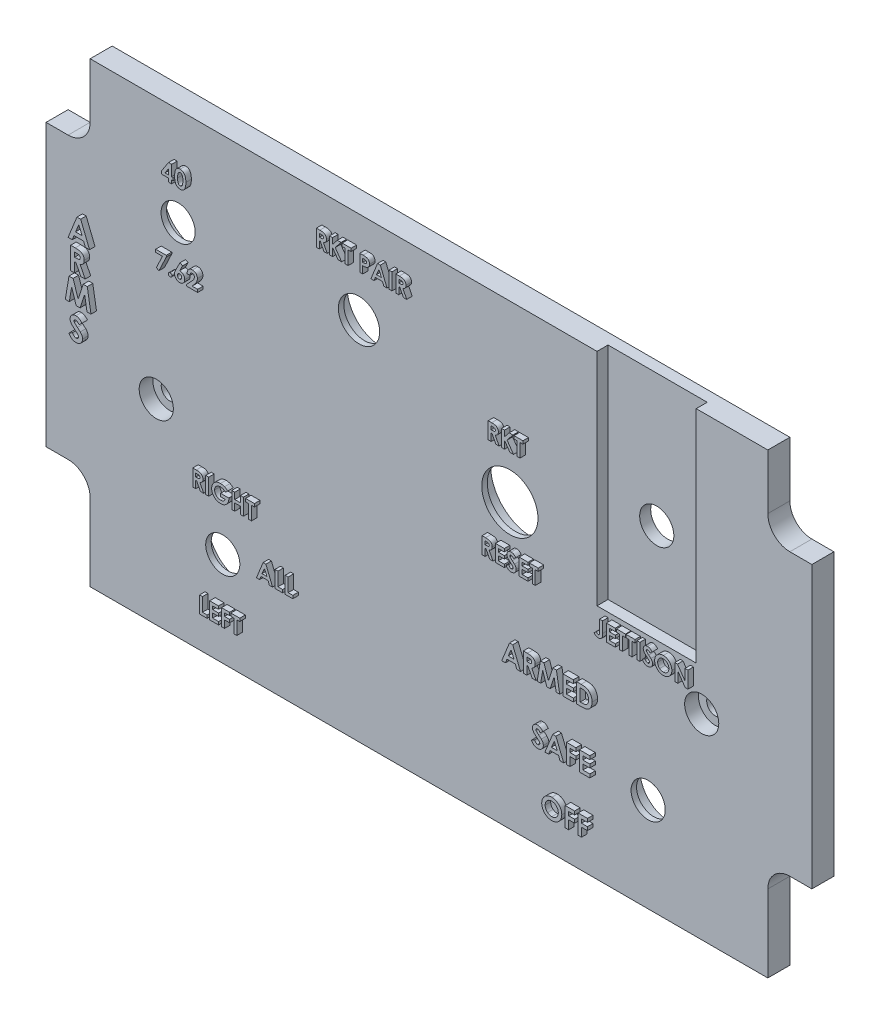
SolidWorks part; units mm, degrees
ref_plane "Front Plane" through (0, 0, 0) normal (0, 0, 1) x (1, 0, 0)
ref_plane "Top Plane" through (0, 0, 0) normal (0, 1, 0) x (1, 0, 0)
ref_plane "Right Plane" through (0, 0, 0) normal (1, 0, 0) x (0, 0, -1)
sketch "Sketch1" plane through (0, 0, 0) normal (0, 0, 1) x (1, 0, 0)
  line L1 (8, 6.6454) -> (131, 6.6454)
  line L2 (0, 24.6454) -> (0, 75.6454)
  line L3 (8, 89.6454) -> (131, 89.6454)
  line L4 (139, 24.6454) -> (139, 75.6454)
  line L13 (8, 89.6454) -> (8, 79.6454)
  line L14 (4, 75.6454) -> (0, 75.6454)
  line L15 (8, 6.6454) -> (8, 20.6454)
  line L16 (4, 24.6454) -> (0, 24.6454)
  line L17 (131, 89.6454) -> (131, 79.6454)
  line L18 (135, 75.6454) -> (139, 75.6454)
  line L19 (131, 6.6454) -> (131, 20.6454)
  line L20 (135, 24.6454) -> (139, 24.6454)
  line L23 (0, 0) -> (0, 87.0008) construction
  arc A8 (8, 20.6454) -> (4, 24.6454) centre (4, 20.6454) ccw
  arc A9 (8, 79.6454) -> (4, 75.6454) centre (4, 79.6454) cw
  arc A11 (131, 20.6454) -> (135, 24.6454) centre (135, 20.6454) cw
  arc A12 (131, 79.6454) -> (135, 75.6454) centre (135, 79.6454) ccw
  circle A14 centre (119, 42.1736) radius 1.6 construction
  circle A15 centre (109.2813, 23.7457) radius 3.1 construction
  circle A16 centre (108.8427, 65.6454) radius 3.1 construction
  circle A17 centre (84.179, 58.026) radius 5.1 construction
  circle A18 centre (56.7976, 72.9728) radius 3.75 construction
  circle A19 centre (32.0701, 23.7457) radius 3.1 construction
  circle A35 centre (20, 42.1736) radius 1.6 construction
  circle A37 centre (23.9669, 71.8931) radius 3.1 construction
  circle A38 centre (119, 42.1736) radius 1.6
  circle A40 centre (109.2813, 23.7457) radius 3.1
  circle A41 centre (108.8427, 65.6454) radius 3.1
  circle A42 centre (84.179, 58.026) radius 5.1
  circle A43 centre (56.7976, 72.9728) radius 3.75
  circle A44 centre (32.0701, 23.7457) radius 3.1
  circle A45 centre (20, 42.1736) radius 1.6
  circle A46 centre (23.9669, 71.8931) radius 3.1
  point P21 (131, 24.6454)
  point P25 (8, 75.6454)
  point P40 (131, 75.6454)
  dimension "D3" = 18
  dimension "D4" = 14
  dimension "D5" = 8
  dimension "D7" = 83
  dimension "D11" = 8
  dimension "D15" = 123
  dimension "D16" = 139
  dimension "D22" = 8
  dimension "D9" = 8
extrude "Boss-Extrude1" add sketch "Sketch1" along normal blind 4
sketch "Sketch5" plane through (0, 0, 0) normal (0, 0, -1) x (-1, 0, 0)
  circle A0 centre (-109.2813, 23.7457) radius 3.1 construction
  circle A1 centre (-108.8427, 65.6454) radius 3.1 construction
  circle A2 centre (-84.179, 58.026) radius 5.1 construction
  circle A3 centre (-56.7976, 72.9728) radius 3.75 construction
  circle A4 centre (-23.9669, 71.8931) radius 3.1 construction
  circle A5 centre (-32.0701, 23.7457) radius 3.1 construction
  circle A6 centre (-109.2813, 23.7457) radius 3.1 construction
  circle A7 centre (-108.8427, 65.6454) radius 3.1 construction
  circle A8 centre (-84.179, 58.026) radius 5.1 construction
  circle A9 centre (-56.7976, 72.9728) radius 3.75 construction
  circle A10 centre (-23.9669, 71.8931) radius 3.1 construction
  circle A11 centre (-32.0701, 23.7457) radius 3.1 construction
  circle A12 centre (-109.2813, 23.7457) radius 5.5
  circle A14 centre (-56.7976, 72.9728) radius 6.15
  circle A17 centre (-84.179, 58.026) radius 7.5
  circle A18 centre (-23.9669, 71.8931) radius 6.75
  circle A19 centre (-32.0701, 23.7457) radius 6.75
  circle A20 centre (-108.8427, 65.6454) radius 6.75
  circle M23 centre (-109.2813, 23.7457) radius 3.1
  circle M25 centre (-84.179, 58.026) radius 5.1
  circle M26 centre (-56.7976, 72.9728) radius 3.75
  circle M27 centre (-32.0701, 23.7457) radius 3.1
  circle M29 centre (-23.9669, 71.8931) radius 3.1
  dimension "D2" = 13.5
  dimension "D3" = 15
  dimension "D4" = 13.5
  dimension "D5" = 13.5
  dimension "D6" = 11
  dimension "D7" = 12.3
  dimension "D1" = 2.4
extrude "Back Holes" cut sketch "Sketch5" against normal blind 3 contours A12 M23 | A17 M25 | A14 M26 | A19 M27 | A18 M29 | A17 region at (114.6257, 23.7457, 0) region at (62.7736, 72.9728, 0) region at (91.4668, 58.026, 0) region at (30.526, 71.8931, 0) region at (38.6292, 23.7457, 0)
sketch "Sketch6" plane through (0, 0, 4) normal (0, 0, 1) x (1, 0, 0)
  circle A0 centre (20, 42.1736) radius 1.6 construction
  circle A1 centre (119, 42.1736) radius 1.6 construction
  circle A2 centre (20, 42.1736) radius 1.6 construction
  circle A3 centre (119, 42.1736) radius 1.6 construction
  circle A4 centre (20, 42.1736) radius 3.1
  circle A5 centre (119, 42.1736) radius 3.1
  dimension "D1" = 1.5
extrude "Cama tornillos" cut sketch "Sketch6" against normal blind 2.5
sketch "Sketch4" plane through (0, 0, 4) normal (0, 0, 1) x (1, 0, 0)
  line L0 (8, 54.5551) -> (8, 14.5758) construction
  line L1 (8, 89.6454) -> (8, 79.6454) construction
  line L2 (-3.2263, 44.852) -> (14.9404, 44.852) construction
  line L4 (-3.2263, 60.566) -> (14.9404, 60.566) construction
  line L5 (-3.2263, 55.566) -> (14.9404, 55.566) construction
  line L6 (-3.2263, 50.566) -> (14.9404, 50.566) construction
  line L7 (5, 54.5551) -> (5, 14.5758) construction
  text T0 "<b>A</b>" font "Century Gothic" height 4
  text T1 "<b>7.62</b>" font "Century Gothic" height 3
  text T2 "<b>RIGHT</b>" font "Century Gothic" height 3
  text T3 "<b>ALL</b>" font "Century Gothic" height 3
  text T4 "<b>RKT</b>" font "Century Gothic" height 3
  text T5 "<b>S</b>" font "Century Gothic" height 4
  text T6 "<b>RESET</b>" font "Century Gothic" height 3
  text T7 "<b>RKT PAIR</b>" font "Century Gothic" height 3
  text T8 "<b>40</b>" font "Century Gothic" height 3
  text T9 "<b>R</b>" font "Century Gothic" height 4
  text T10 "<b>M</b>" font "Century Gothic" height 4
  text T11 "<b>ARMED</b>" font "Century Gothic" height 3.5
  text T12 "<b>SAFE</b>" font "Century Gothic" height 3.5
  text T13 "<b>OFF</b>" font "Century Gothic" height 3.5
  text T14 "<b>LEFT</b>" font "Century Gothic" height 3
  text T15 "<b>JETTISON</b>" font "Century Gothic" height 3
  dimension "D1" = 3
  dimension "D2" = 5
  dimension "D3" = 5
extrude "Textos" add sketch "Sketch4" along normal blind 1
sketch "Sketch8" plane through (0, 0, 4) normal (0, 0, 1) x (1, 0, 0)
  line L0 (131, 79.6454) -> (131, 89.6454) construction
  line L1 (131, 89.6454) -> (8, 89.6454) construction
  line L2 (118, 89.6454) -> (99.9996, 89.6454)
  line L3 (118, 89.6454) -> (118, 49.6454)
  line L4 (118, 49.6454) -> (99.9996, 49.6454)
  line L5 (99.9996, 89.6454) -> (99.9996, 49.6454)
  dimension "D1" = 40
  dimension "D2" = 18.0004
  dimension "D3" = 13
extrude "Cut-Extrude3" cut sketch "Sketch8" against normal blind 2
